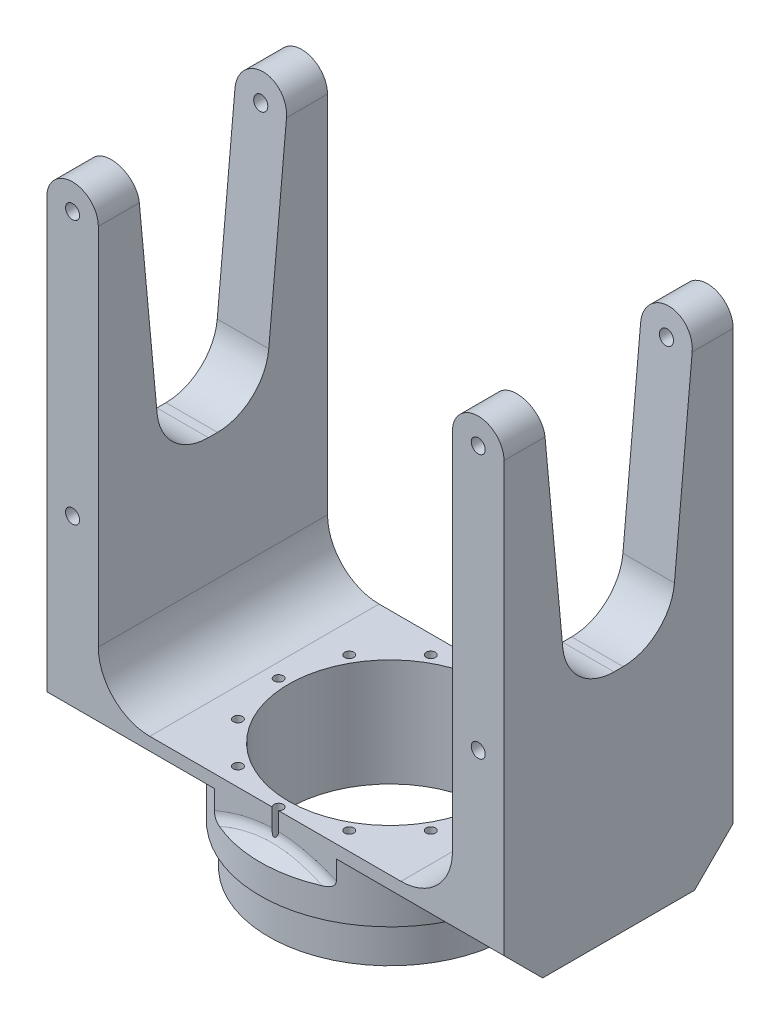
SolidWorks part; units mm, degrees
ref_plane "Front Plane" through (0, 0, 0) normal (0, 0, 1) x (1, 0, 0)
ref_plane "Top Plane" through (0, 0, 0) normal (0, 1, 0) x (1, 0, 0)
ref_plane "Right Plane" through (0, 0, 0) normal (1, 0, 0) x (0, 0, -1)
sketch "Sketch1" plane through (0, 0, 0) normal (0, 0, 1) x (1, 0, 0)
  line L2 (61.15, -65) -> (61.15, -167.5)
  line L3 (-47.5, -167.5) -> (72.5, -167.5) construction
  line L4 (61.15, -167.5) -> (73.85, -167.5)
  line L5 (73.85, -65) -> (73.85, -167.5)
  line L6 (-26.15, -65) -> (-26.15, -167.5)
  line L7 (-38.85, -65) -> (-38.85, -167.5)
  line L8 (-26.15, -167.5) -> (-38.85, -167.5)
  circle A0 centre (-32.5, -130) radius 2.15 construction
  circle A1 centre (67.5, -130) radius 2.15 construction
  circle A2 centre (67.5, -65) radius 2.15 construction
  circle A3 centre (-32.5, -65) radius 2.15 construction
  circle A4 centre (-32.5, -130) radius 2.15 construction
  circle A5 centre (67.5, -130) radius 2.15 construction
  circle A6 centre (67.5, -65) radius 2.15 construction
  circle A7 centre (-32.5, -65) radius 2.15 construction
  circle A8 centre (67.5, -65) radius 1.7272
  circle A9 centre (67.5, -130) radius 1.7272
  circle A10 centre (-32.5, -130) radius 1.7272
  circle A11 centre (-32.5, -65) radius 1.7272
  arc A12 (73.85, -65) -> (61.15, -65) centre (67.5, -65) ccw
  arc A13 (-26.15, -65) -> (-38.85, -65) centre (-32.5, -65) ccw
  dimension "D1" = 3.4544
  dimension "D2" = 12.7
extrude "Boss-Extrude1" add sketch "Sketch1" along normal up to surface (56.5 mm away)
sketch "Sketch2" plane through (0, 0, 0) normal (0, 0, -1) x (-1, 0, 0)
  line L5 (-73.85, -167.5) -> (-61.15, -167.5) construction
  line L6 (38.85, -167.5) -> (-73.85, -167.5)
  line L7 (38.85, -167.5) -> (38.85, -180.2)
  line L8 (38.85, -180.2) -> (-73.85, -180.2)
  line L9 (-73.85, -167.5) -> (-73.85, -180.2)
  dimension "D1" = 12.7
extrude "Boss-Extrude2" add sketch "Sketch2" against normal up to surface (56.5 mm away) up to face at (-34.2272, -65, 56.5)
fillet "Fillet1" radius 12.7 2 edges at (61.15, -167.5, 28.25) (-26.15, -167.5, 28.25)
sketch "Sketch3" plane through (73.85, 0, 0) normal (1, 0, 0) x (0, 0, -1)
  line L0 (-28.25, -58.65) -> (-28.25, -123.65) construction
  line L1 (0, -58.65) -> (-56.5, -58.65) construction
  line L2 (-15.55, -123.65) -> (-40.95, -123.65)
  line L3 (-40.95, -123.65) -> (-46.975, -58.65)
  line L4 (-46.975, -58.65) -> (-9.525, -58.65)
  line L5 (-15.55, -123.65) -> (-9.525, -58.65)
  line L6 (-56.5, -58.65) -> (-56.5, -65) construction
  line L8 (-56.5, -128.2728) -> (-56.5, -131.7272) construction
  line L9 (-56.5, -128.2728) -> (-56.5, -131.7272) construction
  point P13 (-56.5, -130)
  dimension "D1" = 9.525
  dimension "D2" = 25.4
  dimension "D3" = 6.35
extrude "Cut-Extrude1" cut sketch "Sketch3" against normal through all
fillet "Fillet2" radius 12.7 4 edges at (67.5, -123.65, 15.55) (67.5, -123.65, 40.95) (-32.5, -123.65, 40.95) (-32.5, -123.65, 15.55)
chamfer "Chamfer2" distance 9.525 angle 45 2 edges at (17.5, -180.2, 0) (17.5, -180.2, 56.5)
sketch "Sketch5" plane through (0, -180.2, 0) normal (0, -1, 0) x (1, 0, 0)
  line L0 (-38.85, 56.5) -> (73.85, 0) construction
  circle A0 centre (17.5, 28.25) radius 30 construction
  circle A1 centre (17.5, 28.25) radius 32
  dimension "D1" = 60
  dimension "D2" = 2
extrude "Boss-Extrude3" add sketch "Sketch5" along normal blind 4 and the other way offset from surface 3.175 other way up to face at (17.5, -167.5, 28.25)
sketch "Sketch6" plane through (0, -184.2, 0) normal (0, -1, 0) x (1, 0, 0)
  circle A0 centre (17.5, 28.25) radius 29.9
  dimension "D1" = 59.8
extrude "Boss-Extrude4" add sketch "Sketch6" along normal blind 9.8
sketch "Sketch7" plane through (0, -194, 0) normal (0, -1, 0) x (1, 0, 0)
  circle A0 centre (17.5, 28.25) radius 25
  dimension "D1" = 50
extrude "Cut-Extrude2" cut sketch "Sketch7" against normal through all
chamfer "Chamfer3" distance 6.35 angle 45 2 edges at (17.5, -170.675, -3.75) (17.5, -170.675, 60.25)
fillet "Fillet3" radius 3.175 2 edges at (17.5, -173.275, 56.5) (17.5, -173.275, 0)
sketch "Sketch11" plane through (0, -194, 0) normal (0, -1, 0) x (1, 0, 0)
  line L0 (17.5, 58.15) -> (17.5, 53.25) construction
  circle A0 centre (17.5, 28.25) radius 29.9 construction
  circle A1 centre (17.5, 28.25) radius 29.9 construction
  circle A2 centre (17.5, 28.25) radius 25 construction
  circle A4 centre (17.5, 28.25) radius 25 construction
  circle A5 centre (17.5, 28.25) radius 27.45 construction
  circle A6 centre (17.5, 55.7) radius 1.1303
  circle A7 centre (31.225, 52.0224) radius 1.1303
  circle A8 centre (41.2724, 41.975) radius 1.1303
  circle A9 centre (44.95, 28.25) radius 1.1303
  circle A10 centre (41.2724, 14.525) radius 1.1303
  circle A11 centre (31.225, 4.4776) radius 1.1303
  circle A12 centre (17.5, 0.8) radius 1.1303
  circle A13 centre (3.775, 4.4776) radius 1.1303
  circle A14 centre (-6.2724, 14.525) radius 1.1303
  circle A15 centre (-9.95, 28.25) radius 1.1303
  circle A16 centre (-6.2724, 41.975) radius 1.1303
  circle A17 centre (3.775, 52.0224) radius 1.1303
  point P9 (17.5, 55.7)
  point P38 (17.5, 28.25)
  dimension "D1" = 2.2606
  dimension "D2" = 12
extrude "Cut-Extrude4" cut sketch "Sketch11" against normal through all
